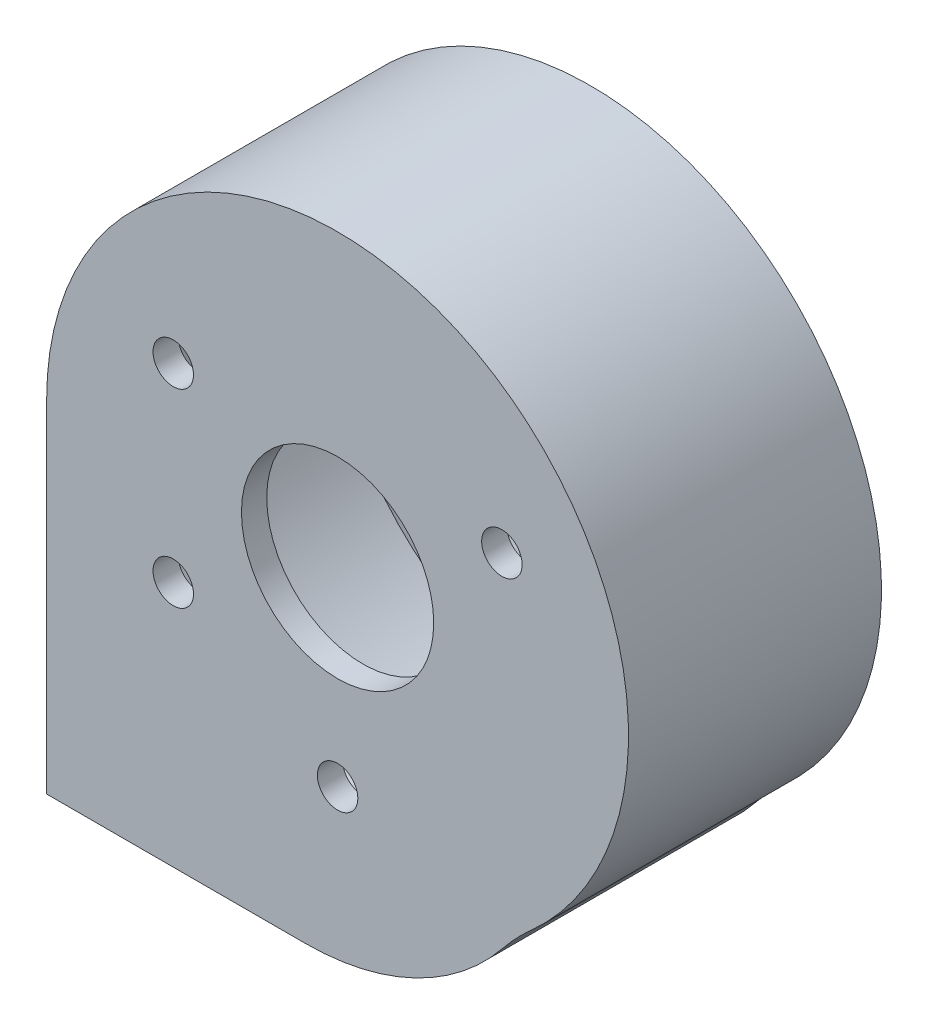
SolidWorks part; units mm, degrees
ref_plane "前视基准面" through (0, 0, 0) normal (0, 0, 1) x (1, 0, 0)
ref_plane "上视基准面" through (0, 0, 0) normal (0, 1, 0) x (1, 0, 0)
ref_plane "右视基准面" through (0, 0, 0) normal (1, 0, 0) x (0, 0, -1)
other "Configuration Table"
sketch "草图1" plane through (0, 0, 0) normal (0, 0, 1) x (1, 0, 0)
  line L4 (-23, 0) -> (-23, -27)
  line L5 (-23, -27) -> (-2.527, -27)
  circle A0 centre (12.9904, 7.5) radius 1.6
  circle A2 centre (0, -15) radius 1.6
  circle A3 centre (-12.9904, -7.5) radius 1.6
  circle A4 centre (-12.9904, 7.5) radius 1.6
  arc A6 (15.3161, -17.1586) -> (13.0537, -19.5395) centre (28.6345, -32.079) ccw
  arc A7 (15.3161, -17.1586) -> (-23, 0) centre (0, 0) ccw
  arc A8 (-2.527, -27) -> (13.0537, -19.5395) centre (-2.527, -7) ccw
  circle A9 centre (0, 0) radius 7.6
  dimension "D1" = 15.2
extrude "凸台-拉伸1" add sketch "草图1" along normal blind 20
sketch "草图3" plane through (0, 0, 0) normal (0, 0, -1) x (-1, 0, 0)
  circle A0 centre (0, 0) radius 21.1
  dimension "D1" = 42.2
extrude "切除-拉伸11" cut sketch "草图3" against normal blind 18
sketch "草图4" plane through (0, 0, 0) normal (0, 0, -1) x (-1, 0, 0)
  line L0 (23, 0) -> (23, -27) construction
  line L6 (2.527, -27) -> (2.527, -24)
  line L8 (23, -27) -> (23, -24)
  line L15 (23, -27) -> (23, -14.7847)
  line L16 (23, -14.7847) -> (19.0735, -14.7847)
  line L18 (2.527, -27) -> (23, -27)
  arc A1 (2.527, -24) -> (19.0735, -14.7847) centre (0, 0) ccw
  line M8 (2.527, -27) -> (23, -27)
  line M9 (23, -27) -> (23, 0)
  dimension "D1" = 3
extrude "凸台-拉伸2" add sketch "草图4" along normal blind 20 contours A1 L6 L16 M8 M9 region at (-15.4377, -22.5793, 0)
fillet "圆角3" radius 3 3 edges at (-2.527, -25.5, 0) (-21.0367, -14.7847, 0) (-11.7421, -21.0834, 0)
sketch "草图5" plane through (0, -27, 0) normal (0, -1, 0) x (1, 0, 0)
  line L0 (-23, 20) -> (-2.527, 20) construction
  line L1 (-23, 20) -> (-23, -20) construction
  line L2 (-2.527, 20) -> (-2.527, -3) construction
  line L3 (-28.9905, 0) -> (25.7032, 0) construction
  circle A0 centre (-18, 15) radius 1.5
  circle A1 centre (-6.527, 15) radius 1.5
  circle A2 centre (-6.527, -15) radius 1.5
  circle A3 centre (-18, -15) radius 1.5
  dimension "D1" = 5
  dimension "D3" = 4
  dimension "D2" = 5
extrude "切除-拉伸12" cut sketch "草图5" against normal blind 5
